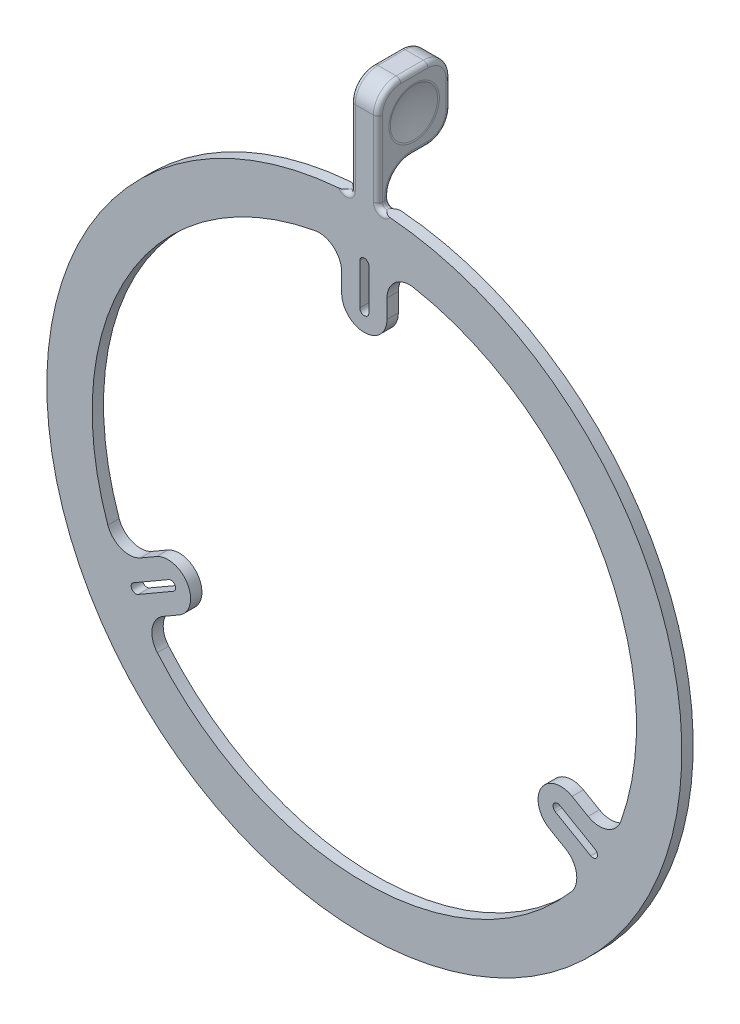
SolidWorks part; units mm, degrees
ref_plane "Front Plane" through (0, 0, 0) normal (0, 0, 1) x (1, 0, 0)
ref_plane "Top Plane" through (0, 0, 0) normal (0, 1, 0) x (1, 0, 0)
ref_plane "Right Plane" through (0, 0, 0) normal (1, 0, 0) x (0, 0, -1)
sketch "Sketch2" plane through (0, 0, 0) normal (0, 0, 1) x (1, 0, 0)
  circle A0 centre (0, 0) radius 120
  circle A1 centre (0, 0) radius 150
  dimension "D1" = 240
  dimension "D2" = 300
extrude "Boss-Extrude1" add sketch "Sketch2" along normal blind 5
sketch "Sketch3" plane through (0, 0, 5) normal (0, 0, 1) x (1, 0, 0)
  line L0 (10, 100) -> (10, 119.5826)
  line L1 (-10, 100) -> (-10, 119.5826)
  line L2 (0, 98.406) -> (0, 116.406) construction
  line L3 (-2, 98.406) -> (-2, 116.406)
  line L4 (2, 98.406) -> (2, 116.406)
  circle A0 centre (0, 100) radius 10
  circle A1 centre (0, 0) radius 120 construction
  arc A2 (-2, 98.406) -> (2, 98.406) centre (0, 98.406) ccw
  arc A3 (2, 116.406) -> (-2, 116.406) centre (0, 116.406) ccw
  point P11 (0, 107.406)
  circle M3 centre (0, 0) radius 120
  dimension "D1" = 20
  dimension "D2" = 100
extrude "Boss-Extrude2" add sketch "Sketch3" against normal up to surface (5 mm away) contours A0 | A0 L0 M3 region at (7.9651, 106.5034, 5) region at (0, 90.2814, 5) up to face at (150, 0, 0)
fillet "Fillet1" radius 10 2 edges at (10, 119.5826, 2.5) (-10, 119.5826, 2.5)
pattern_circular "CirPattern1" count 3 every 120 about axis through (0, 0, 5) along (0, 0, 1) of "Boss-Extrude2", "Fillet1"
sketch "Sketch5" plane through (0, 0, 5) normal (0, 0, 1) x (1, 0, 0)
  line L0 (0, 150) -> (0, 185)
  line L1 (-6, 185) -> (6, 185)
  line L2 (6, 185) -> (6, 149.88)
  line L3 (-6, 185) -> (-6, 149.88)
  line L4 (-6, 149.88) -> (-6, 153.9098)
  line L5 (-6, 153.9098) -> (6, 153.9098)
  line L6 (6, 153.9098) -> (6, 149.88)
  circle A0 centre (0, 0) radius 150 construction
  circle A1 centre (0, 0) radius 150
  point P9 (0, 185)
  circle M3 centre (0, 0) radius 150
  dimension "D1" = 12
  dimension "D2" = 35
extrude "Boss-Extrude4" add sketch "Sketch5" against normal up to surface (5 mm away) contours L3 L5 L0 L1 | L0 L5 L2 L1 | L5 L3 L0 M3 | L5 L0 L2 M3 region at (-3.0152, 151.9347, 5) region at (3.0152, 151.9347, 5) region at (-3, 169.4549, 5) region at (3, 169.4549, 5) up to face at (150, 0, 0)
sketch "Sketch12" plane through (0, 0, 0) normal (0, 0, -1) x (-1, 0, 0)
  line L0 (6, 149.88) -> (6, 185) construction
  line L1 (-6, 185) -> (6, 185)
  line L2 (-6, 185) -> (-6, 153)
  line L3 (-6, 153) -> (6, 153)
  line L4 (6, 185) -> (6, 153)
  dimension "D1" = 32
extrude "Boss-Extrude5" add sketch "Sketch12" along normal blind 27
ref_plane "Plane5" through (0, 169, 0) normal (0, 1, 0) x (1, 0, 0)
sketch "Sketch13" plane through (0, 169, 0) normal (0, 1, 0) x (1, 0, 0)
  line L0 (6, 27) -> (6, -5) construction
  line L1 (6, 11) -> (6, 0.2297)
  line L2 (6, 11) -> (4, 11)
  arc A0 (4, 11) -> (6, 0.2297) centre (34, 11) ccw
  dimension "D3" = 30
  dimension "D1" = 2
revolve "Cut-Revolve4" cut sketch "Sketch13" angle 360 about L2
ref_plane "Plane6" through (0, 0, 0) normal (-1, 0, 0) x (0, 0, 1)
mirror "Mirror2" about plane through (0, 0, 0) normal (-1, 0, 0) of "Cut-Revolve4"
sketch "Sketch14" plane through (-6, 0, 0) normal (-1, 0, 0) x (0, 0, 1)
  line L0 (0, 149.88) -> (0, 153) construction
  line L1 (0, 149.88) -> (0, 153)
  line L2 (0, 153) -> (-10, 153)
  line L3 (-27, 153) -> (0, 153) construction
  line L4 (0, 153) -> (0, 143)
  arc A0 (0, 143) -> (-10, 153) centre (-10, 143) ccw
  dimension "D1" = 10
  dimension "D2" = 10
extrude "Boss-Extrude6" add sketch "Sketch14" against normal up to surface (12 mm away) contours L4 A0 L2 up to face at (6, 169, -21.7703)
sketch "Sketch15" plane through (0, 0, 5) normal (0, 0, 1) x (1, 0, 0)
  line L0 (-6, 149.88) -> (-6, 139.8714)
  line L1 (6, 149.88) -> (6, 139.8714)
  circle A0 centre (0, 0) radius 140
  circle A1 centre (0, 0) radius 150
  arc M5 (-6, 149.88) -> (6, 149.88) centre (0, 0) ccw
  dimension "D1" = 280
extrude "Cut-Extrude1" cut sketch "Sketch15" against normal up to surface (5 mm away) contours A0 L0 L1 M5 region at (-10.2418, 144.8757, 5) up to face at (93.0163, -53.703, 0)
fillet "Fillet19" radius 10 3 edges at (0, 185, 5) (0, 185, -27) (0, 153, -27)
fillet "Fillet24" radius 2 22 edges at (6, 169, -21.7703) (6, 182.0711, -24.0711) (6, 169, -27) (6, 155.9289, -24.0711) (6, 153, -13.5) (6, 150.0711, -2.9289) (6, 141.4357, 0) (6, 139.8714, 2.5) (6, 157.4357, 5) (6, 182.0711, 2.0711) (6, 185, -11) (-6, 169, -21.7703) (-6, 139.8714, 2.5) (-6, 141.4357, 0) (-6, 150.0711, -2.9289) (-6, 153, -13.5) (-6, 155.9289, -24.0711) (-6, 169, -27) (-6, 182.0711, -24.0711) (-6, 185, -11) (-6, 182.0711, 2.0711) (-6, 157.4357, 5) tangent propagation no
